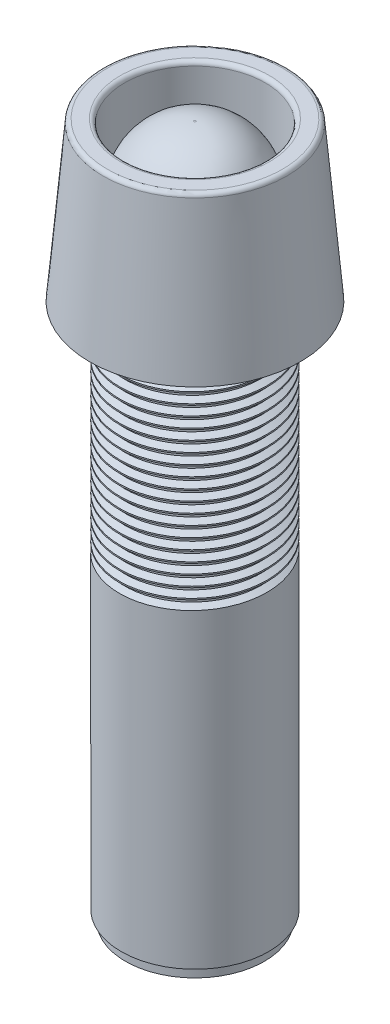
SolidWorks part; units mm, degrees
ref_plane "Спереди" through (0, 0, 0) normal (0, 0, 1) x (1, 0, 0)
ref_plane "Сверху" through (0, 0, 0) normal (0, 1, 0) x (1, 0, 0)
ref_plane "Справа" through (0, 0, 0) normal (1, 0, 0) x (0, 0, -1)
sketch "Эскиз1" plane through (0, 0, 0) normal (0, 1, 0) x (1, 0, 0)
  circle A0 centre (0, 0) radius 3.5
  dimension "D1" = 7
extrude "Бобышка-Вытянуть1" add sketch "Эскиз1" against normal blind 25
sketch "Эскиз2" plane through (0, -25, 0) normal (0, -1, 0) x (1, 0, 0)
  circle A3 centre (0, 0) radius 3.3
  circle A4 centre (0, 0) radius 3.3
  dimension "D1" = 0.2
extrude "Бобышка-Вытянуть2" add sketch "Эскиз2" along normal blind 0.5
sketch "Эскиз4" plane through (0, 0, 0) normal (0, 1, 0) x (1, 0, 0)
  circle A0 centre (0, 0) radius 5
  dimension "D1" = 10
extrude "Бобышка-Вытянуть3" add sketch "Эскиз4" along normal blind 7.5 draft 5 contours A0
thread "Резьба1" pitch 0.5 method cut profile "Профиль резьбы1" start angle 0, offset 0, length 10, pitch 0.5, diameter 7
ref_plane "Плоскость1" through (-3.5, 0, 0) normal (0, 0, 1) x (-1, 0, 0)
sketch "Профиль резьбы1" plane through (-3.5, 0, 0) normal (0, 0, 1) x (-1, 0, 0)
  line L0 (0, 0) -> (0, 0.5) construction
  line L11 (0, 0) -> (0, 0.4375)
  line L12 (0, 0.4375) -> (-0.2706, 0.2812)
  line L13 (-0.2706, 0.2812) -> (-0.2706, 0.1562)
  line L15 (-0.2706, 0.1562) -> (0, 0)
  line L17 (-0.2706, 0.2187) -> (0, 0.2187) construction
  point P2 (0, 0)
  dimension "Pitch" = 0.5
  dimension "Profile_Angle" = 60
  dimension "Profile_Land" = 0.125
  dimension "Profile_Height" = 0.2706
sketch "Эскиз9" plane through (0, 7.5, 0) normal (0, 1, 0) x (1, 0, 0)
  circle A2 centre (0, 0) radius 3.3438
  circle A3 centre (0, 0) radius 3.3438
  dimension "D1" = 1
extrude "Вырез-Вытянуть1" cut sketch "Эскиз9" against normal blind 5
fillet "Скругление1" radius 0.2 2 edges at (0, 7.5, 3.3438) (0, 7.5, 4.3438)
sketch "Эскиз10" plane through (0, 2.5, 0) normal (0, 1, 0) x (1, 0, 0)
  circle A1 centre (0, 0) radius 3.3438
  circle A2 centre (0, 0) radius 3.3438
  dimension "D1" = 0
extrude "Бобышка-Вытянуть4" add sketch "Эскиз10" along normal blind 4.9 draft 8
fillet "Скругление2" radius 3 1 edges at (0, 7.4, 2.6552)
